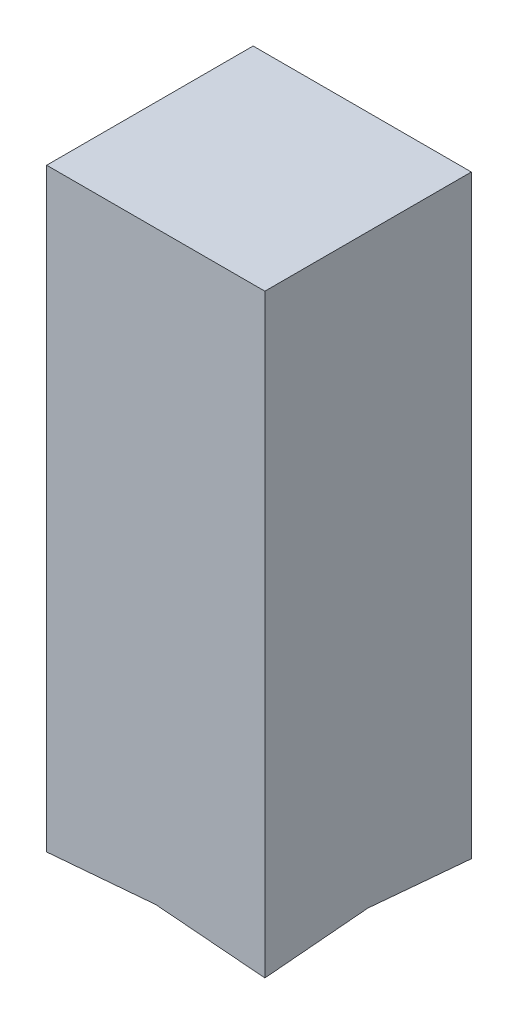
SolidWorks part; units mm, degrees
material "K110"
ref_plane "Front Plane" through (0, 0, 0) normal (0, 0, 1) x (1, 0, 0)
ref_plane "Top Plane" through (0, 0, 0) normal (0, 1, 0) x (1, 0, 0)
ref_plane "Right Plane" through (0, 0, 0) normal (1, 0, 0) x (0, 0, -1)
sketch "Sketch1" plane through (0, 0, 0) normal (0, 1, 0) x (1, 0, 0)
  line L1 (-10.125, -9.58) -> (10.125, -9.58)
  line L2 (-10.125, -9.58) -> (-10.125, 9.58)
  line L3 (-10.125, 9.58) -> (10.125, 9.58)
  line L4 (10.125, -9.58) -> (10.125, 9.58)
  line L5 (-10.125, -9.58) -> (10.125, 9.58) construction
  line L6 (-10.125, 9.58) -> (10.125, -9.58) construction
  point P0 (0, 0)
  dimension "D1" = 19.16
  dimension "D2" = 20.25
extrude "Boss-Extrude1" add sketch "Sketch1" against normal blind 55.2
sketch "Sketch5" plane through (10.125, 0, 0) normal (1, 0, 0) x (0, 0, -1)
  line L0 (-9.58, -55.2) -> (0, -54.3619)
  line L1 (0, -54.3619) -> (9.58, -55.2)
  line L2 (9.58, -55.2) -> (-9.58, -55.2)
  point P3 (0, 0)
  dimension "D1" = 5
extrude "Cut-Extrude2" cut sketch "Sketch5" against normal through all
sketch "Sketch6" plane through (0, 0, 9.58) normal (0, 0, 1) x (1, 0, 0)
  line L0 (-10.125, -55.2) -> (0, -54.3619)
  line L1 (-10.125, -54.3619) -> (10.125, -54.3619) construction
  line L2 (0, -54.3619) -> (10.125, -55.2)
  line L3 (10.125, -55.2) -> (-10.125, -55.2)
  dimension "D1" = 4.732
extrude "Cut-Extrude3" cut sketch "Sketch6" against normal through all
